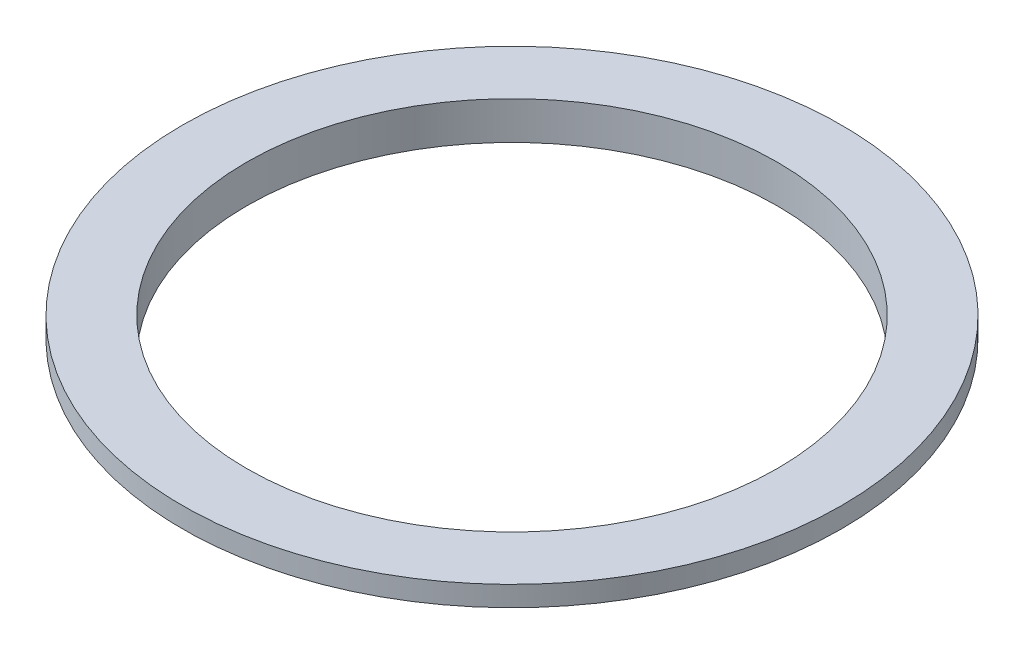
SolidWorks part; units mm, degrees
material "PET"
ref_plane "Front Plane" through (0, 0, 0) normal (0, 0, 1) x (1, 0, 0)
ref_plane "Top Plane" through (0, 0, 0) normal (0, 1, 0) x (1, 0, 0)
ref_plane "Right Plane" through (0, 0, 0) normal (1, 0, 0) x (0, 0, -1)
sketch "Sketch2" plane through (0, 0, 0) normal (0, 0, 1) x (1, 0, 0)
  line L0 (-55, 8.3) -> (-52.5, 8.3)
  line L1 (-52.5, 8.3) -> (-52.5, 15.8)
  line L2 (-52.5, 15.8) -> (-65.2, 15.8)
  line L3 (-65.2, 15.8) -> (-65.2, 11.8)
  line L4 (-65.2, 11.8) -> (-55, 11.8)
  line L5 (-55, 11.8) -> (-55, 8.3)
  line L11 (0, 0) -> (0, 30.013) construction
sketch "Sketch3" plane through (0, 0, 0) normal (0, 0, 1) x (1, 0, 0)
  line L6 (-55, 8.3) -> (-52.5, 8.3)
  line L7 (-52.5, 8.3) -> (-52.5, 15.8)
  line L8 (-52.5, 15.8) -> (-65.2, 15.8)
  line L9 (-65.2, 15.8) -> (-65.2, 11.8)
  line L10 (-65.2, 11.8) -> (-55, 11.8)
  line L11 (-55, 11.8) -> (-55, 8.3)
  line L12 (-55, 8.3) -> (-52.5, 8.3)
  line L13 (-52.5, 8.3) -> (-52.5, 15.8)
  line L14 (-52.5, 15.8) -> (-65.2, 15.8)
  line L15 (-65.2, 15.8) -> (-65.2, 11.8)
  line L16 (-65.2, 11.8) -> (-55, 11.8)
  line L17 (-55, 11.8) -> (-55, 8.3)
  dimension "D1" = 0
revolve "Cap" add sketch "Sketch3" angle 360 about L11
